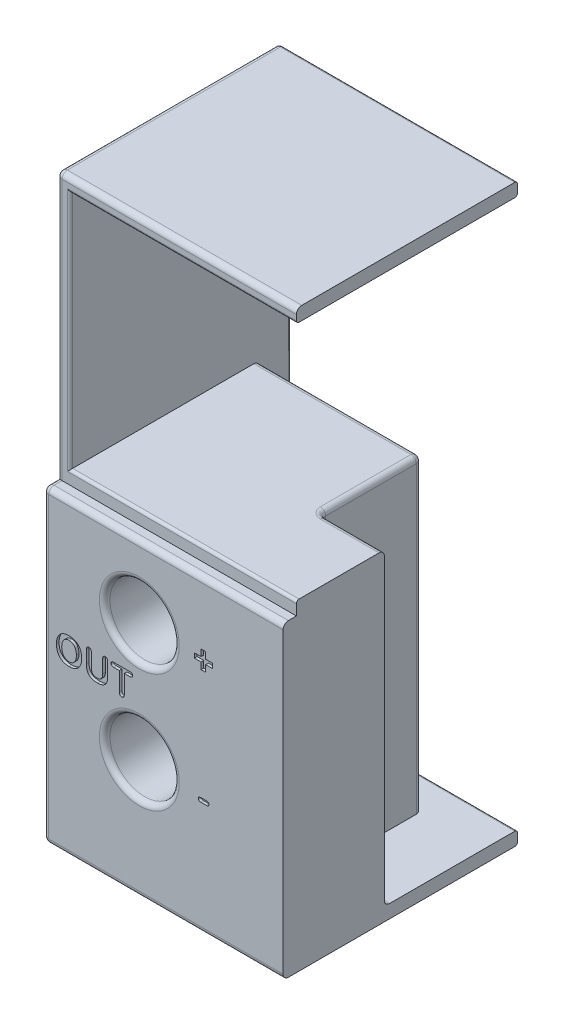
SolidWorks part; units mm, degrees
ref_plane "Front Plane" through (0, 0, 0) normal (0, 0, 1) x (1, 0, 0)
ref_plane "Top Plane" through (0, 0, 0) normal (0, 1, 0) x (1, 0, 0)
ref_plane "Right Plane" through (0, 0, 0) normal (1, 0, 0) x (0, 0, -1)
sketch "Sketch2" plane through (0, 0, 0) normal (0, 0, 1) x (1, 0, 0)
  line L0 (0, 32.5) -> (0, 0) construction
  line L1 (43.9999, -54) -> (-43.9999, -54)
  line L2 (43.9999, -54) -> (43.9999, 54)
  line L3 (43.9999, 54) -> (-43.9999, 54)
  line L4 (-43.9999, -54) -> (-43.9999, 54)
  line L5 (43.9999, -54) -> (-43.9999, 54) construction
  line L6 (43.9999, 54) -> (-43.9999, -54) construction
  line L9 (0, 0) -> (0, -20.5) construction
  line L10 (-31.75, 43.125) -> (31.75, 43.125)
  line L11 (-31.75, 43.125) -> (-31.75, 21.875)
  line L12 (-31.75, 21.875) -> (31.75, 21.875)
  line L13 (31.75, 43.125) -> (31.75, 21.875)
  line L14 (-31.75, 43.125) -> (31.75, 21.875) construction
  line L15 (-31.75, 21.875) -> (31.75, 43.125) construction
  line L16 (27, -31.625) -> (-27, -31.625)
  line L17 (27, -31.625) -> (27, -9.375)
  line L18 (27, -9.375) -> (-27, -9.375)
  line L19 (-27, -31.625) -> (-27, -9.375)
  line L20 (27, -31.625) -> (-27, -9.375) construction
  line L21 (27, -9.375) -> (-27, -31.625) construction
  circle A0 centre (-27, -9.375) radius 6.5
  circle A1 centre (27, -9.375) radius 6.5
  circle A2 centre (27, -31.625) radius 6.5
  circle A3 centre (-27, -31.625) radius 6.5
  point P0 (0, 0)
  point P5 (0, 32.5)
  point P26 (0, -20.5)
  dimension "D4" = 13
  dimension "D1" = 108
  dimension "D2" = 21.25
  dimension "D3" = 63.5
  dimension "D5" = 22.25
  dimension "D6" = 54
  dimension "D7" = 87.9997
  dimension "D8" = 32.5
  dimension "D9" = 20.5
extrude "Boss-Extrude1" add sketch "Sketch2" against normal blind 46 contours L4 L1 L2 L3 A3 L19 A0 L18 A1 L17 A2 L16 L10 L13 L12 L11 | A3 L16 A2 L17 A1 L18 A0 L19 region at (0, -1.6874, 0) region at (0, -20.5, 0)
sketch "Sketch3" plane through (0, 0, 0) normal (1, 0, 0) x (0, 0, -1)
  line L0 (46, -54) -> (0, -54) construction
  line L1 (46, 54) -> (0.0001, 54)
  line L2 (46, 54) -> (46, -54)
  line L3 (46, -54) -> (0.0001, -54)
  line L4 (0.0001, 54) -> (0.0001, -54)
  line L5 (46, 54) -> (0.0001, -54) construction
  line L6 (46, -54) -> (0.0001, 54) construction
  line L7 (46, -54) -> (46, 54) construction
  line L8 (23, -15.875) -> (23, -25.125) construction
  line L9 (30.5308, -2.875) -> (30.5308, -15.875) construction
  line L18 (34, 0.625) -> (34, -19.375)
  line L19 (34, -9.375) -> (27.5, -9.375) construction
  line L20 (36, -19.375) -> (34, -19.375)
  line L21 (36, 0.625) -> (36, -19.375)
  line L22 (36, 0.625) -> (34, 0.625)
  line L23 (34, -19.375) -> (34, 0.625)
  line L24 (19, 0.625) -> (34, 0.625)
  line L25 (19, -19.375) -> (19, 0.625)
  line L26 (19, -19.375) -> (34, -19.375)
  line L27 (46, -2.875) -> (0, -2.875) construction
  line L28 (0, -15.875) -> (46, -15.875) construction
  line L29 (46, -25.125) -> (0, -25.125) construction
  line L30 (0.0001, -20.5) -> (46, -20.5) construction
  line L31 (34, -31.625) -> (27.5, -31.625) construction
  line L32 (30.5308, -38.125) -> (30.5308, -25.125) construction
  line L33 (19, -21.625) -> (34, -21.625)
  line L34 (19, -21.625) -> (19, -41.625)
  line L35 (19, -41.625) -> (34, -41.625)
  line L36 (34, -21.625) -> (34, -41.625)
  line L37 (36, -41.625) -> (34, -41.625)
  line L38 (36, -41.625) -> (36, -21.625)
  line L39 (36, -21.625) -> (34, -21.625)
  line L40 (34, -41.625) -> (34, -21.625)
  arc A1 (34, -17.625) -> (34, -1.125) centre (35.9856, -9.375) cw
  arc A2 (34, -23.375) -> (34, -39.875) centre (35.9856, -31.625) ccw
  point P0 (23, 0)
  point P8 (30.5308, -9.375)
  point P19 (23, -20.5)
  point P48 (23, -41)
  dimension "D4" = 6.5
  dimension "D7" = 1.75
  dimension "D1" = 108
  dimension "D2" = 20
  dimension "D3" = 45.9999
  dimension "D5" = 2
  dimension "D6" = 15
  dimension "D8" = 10
sketch "Sketch4" plane through (0, 0, -46) normal (0, 0, -1) x (-1, 0, 0)
  line L1 (-31.75, 21.875) -> (31.75, 21.875)
  line L2 (-31.75, 21.875) -> (-31.75, 43.125)
  line L3 (-31.75, 43.125) -> (31.75, 43.125)
  line L4 (31.75, 21.875) -> (31.75, 43.125)
extrude "Boss-Extrude2" add sketch "Sketch4" against normal offset from surface (44 mm away) 2 up to face at (-20.5, -9.375, 0)
sketch "Sketch5" plane through (0, 0, -46) normal (0, 0, -1) x (-1, 0, 0)
  circle A0 centre (-27, -9.375) radius 6.5
  circle A1 centre (-27, -31.625) radius 6.5
  circle A2 centre (27, -31.625) radius 6.5
  circle A3 centre (27, -9.375) radius 6.5
  circle A5 centre (-27, -9.375) radius 6.5 construction
extrude "Boss-Extrude3" add sketch "Sketch5" against normal blind 10
sketch "Sketch7" plane through (0, 0, 0) normal (0, 0, 1) x (1, 0, 0)
  line L0 (-45, -54) -> (45, 54) construction
  line L1 (-45, 54) -> (45, 54)
  line L2 (-45, 54) -> (-45, -54)
  line L3 (-45, -54) -> (45, -54)
  line L4 (45, 54) -> (45, -54)
  line L5 (43.9999, 54) -> (-43.9999, 54) construction
  line L7 (-43.9999, 54) -> (43.9999, 54)
  line L8 (-43.9999, 54) -> (-43.9999, -54)
  line L9 (-43.9999, -54) -> (43.9999, -54)
  line L10 (43.9999, 54) -> (43.9999, -54)
  line M10 (-43.9999, 54) -> (-43.9999, -54)
  line M12 (43.9999, -54) -> (43.9999, 54)
  dimension "D1" = 90
extrude "Boss-Extrude4" add sketch "Sketch7" against normal up to surface (46 mm away) contours L0 L3 L4 M12 | L2 L0 L1 M10 | L10 L0 L1 | L0 L3 L8 region at (-44.5009, 0.2995, 0) region at (-44.3332, -53.5999, 0) region at (44.3332, 53.5999, 0) region at (44.5009, -0.2995, 0) up to face at (0, 0, -46)
extrude "Cut-Extrude1" cut sketch "Sketch3" along normal blind 28 from surface contours L18 A1 L24 L25 L26 | L21 L22 L18 L23 L20 | A2 L36 L33 L34 L35 | L40 A2 | L38 L39 L36 L40 L37 | A1 L23 region at (0, -9.375, -35) region at (0, -9.375, -24.7667) region at (0, -9.375, -31.2897) region at (0, -31.625, -24.7667) region at (0, -31.625, -35) region at (0, -31.625, -31.2897) starting at face at (-45, 0, -23)
extrude "Cut-Extrude2" cut sketch "Sketch3<3>" against normal blind 28 from surface contours L18 A1 L24 L25 L26 | A1 L23 | L21 L22 L18 L23 L20 | L38 L39 L36 L40 L37 | L40 A2 | A2 L36 L33 L34 L35 region at (0, -9.375, -35) region at (0, -9.375, -24.7667) region at (0, -9.375, -31.2897) region at (0, -31.625, -24.7667) region at (0, -31.625, -35) region at (0, -31.625, -31.2897) starting at face at (45, 0, -23)
sketch "Sketch3<3>" plane through (0, 0, 0) normal (1, 0, 0) x (0, 0, -1) same geometry as "Sketch3"
sketch "Sketch6" plane through (0, 0, 0) normal (0, 0, 1) x (1, 0, 0)
  line L1 (-42.5, 51.5) -> (42.5, 51.5)
  line L2 (-42.5, 51.5) -> (-42.5, 6.5)
  line L3 (-42.5, 6.5) -> (42.5, 6.5)
  line L4 (42.5, 51.5) -> (42.5, 6.5)
  line L5 (-42.5, 51.5) -> (42.5, 6.5) construction
  line L6 (-45, 54) -> (45, 54)
  line L7 (-45, 54) -> (-45, 4)
  line L8 (-45, 4) -> (45, 4)
  line L9 (45, 54) -> (45, 4)
  line L10 (45, 54) -> (-45, 4) construction
  point P9 (0, 29)
  line M13 (-31.75, 43.125) -> (31.75, 43.125)
  line M14 (31.75, 43.125) -> (31.75, 21.875)
  line M15 (31.75, 21.875) -> (-31.75, 21.875)
  line M16 (-31.75, 21.875) -> (-31.75, 43.125)
  dimension "D1" = 85
  dimension "D2" = 45
  dimension "D3" = 90
  dimension "D4" = 50
extrude "Cut-Extrude4" cut sketch "Sketch6" against normal through all contours L4 L1 L2 L3 M16 M13 M14 M15 | M13 M16 M15 M14 region at (0, 50.5382, 0) region at (0, 32.5, 0)
sketch "Sketch8" plane through (0, 0, -36) normal (0, 0, 1) x (1, 0, 0)
  circle A0 centre (-27, -9.375) radius 4.25
  circle A1 centre (-27, -31.625) radius 4.25
  circle A2 centre (27, -31.625) radius 4.25
  circle A3 centre (27, -9.375) radius 4.25
  circle A4 centre (27, -31.625) radius 6.5 construction
  circle A5 centre (27, -9.375) radius 6.5 construction
  circle A6 centre (-27, -9.375) radius 6.5 construction
  circle A7 centre (-27, -31.625) radius 6.5 construction
  dimension "D1" = 8.5
extrude "Cut-Extrude5" cut sketch "Sketch8" against normal through all
sketch "Sketch9" plane through (0, 0, -46) normal (0, 0, -1) x (-1, 0, 0)
  line L0 (0, -51.5) -> (0, -54) construction
  line L1 (-42.5, 51.5) -> (42.5, 51.5)
  line L2 (-42.5, 51.5) -> (-42.5, -51.5)
  line L3 (-42.5, -51.5) -> (42.5, -51.5)
  line L4 (42.5, 51.5) -> (42.5, -51.5)
  line L5 (-45, -54) -> (45, -54) construction
  line L6 (42.5, 0) -> (45, 0) construction
  line L7 (45, -54) -> (45, 54) construction
extrude "Cut-Extrude6" cut sketch "Sketch9" against normal blind 8
extrude "Cut-Extrude7" cut sketch "Sketch6<4>" against normal blind 2.5
sketch "Sketch6<4>" plane through (0, 0, 0) normal (0, 0, 1) x (1, 0, 0) same geometry as "Sketch6"
sketch "Sketch10" plane through (0, 0, 0) normal (1, 0, 0) x (0, 0, -1)
  line L0 (46, -54) -> (0, -54) construction
  line L1 (46, 54) -> (44, 54)
  line L2 (46, 54) -> (46, -54)
  line L3 (46, -54) -> (44, -54)
  line L4 (44, 54) -> (44, -54)
  dimension "D1" = 2
extrude "Cut-Extrude8" cut sketch "Sketch10" against normal through all both and the other way through all
fillet "Fillet2" radius 1 74 edges at (-45, -41.625, -27.5) (-45, -21.625, -27.5) (-45, -19.375, -27.5) (-45, 0.625, -27.5) (-17, -19.375, -27.5) (-17, 0.625, -27.5) (-31, -21.625, -36) (-31, -41.625, -36) (-45, -31.625, -36) (-22.75, -31.625, -36) (-31, 0.625, -36) (-17, -9.375, -36) (-31, -19.375, -36) (-45, -9.375, -36) (-22.75, -9.375, -36) (-17, -41.625, -27.5) (-17, -31.625, -36) (-17, -21.625, -27.5) (-27, -38.125, -19) (-31, -41.625, -19) (-17, -31.625, -19) (-31, -21.625, -19) (-45, -31.625, -19) (-27, -2.875, -19) (-31, -19.375, -19) (-17, -9.375, -19) (-31, 0.625, -19) (-45, -9.375, -19) (45, -19.375, -27.5) (27, -2.875, -19) (31, -19.375, -19) (45, -9.375, -19) (17, -19.375, -27.5) (17, -9.375, -19) (17, 0.625, -27.5) (31, 0.625, -19) (45, 0.625, -27.5) (31, -19.375, -36) (17, -9.375, -36) (31, 0.625, -36) (45, -9.375, -36) (31.25, -9.375, -36) (45, -41.625, -27.5) (31, -41.625, -36) (45, -31.625, -36) (31.25, -31.625, -36) (31, -21.625, -36) (45, -21.625, -27.5) (27, -38.125, -19) (31, -21.625, -19) (31, -41.625, -19) (45, -31.625, -19) (17, -31.625, -19) (17, -21.625, -27.5) (17, -31.625, -36) (17, -41.625, -27.5) (0, 6.5, -38) (45, -54, -22) (-45, -54, -22) (-45, 54, -23.25) (-45, 4, -1.25) (-45, 29, -2.5) (-45, -25, 0) (0, -54, 0) (0, 4, 0) (45, 4, -1.25) (45, -25, 0) (45, 54, -23.25) (45, 29, -2.5) (0, 54, -2.5) (-20.5, -31.625, 0) (33.5, -9.375, 0) (33.5, -31.625, 0) (-20.5, -9.375, 0)
fillet "Fillet3" radius 0.5 20 edges at (44.7071, 53.7071, -44) (0, 54, -44) (-44.7071, 53.7071, -44) (-45, 0, -44) (-44.7071, -53.7071, -44) (0, -54, -44) (44.7071, -53.7071, -44) (45, 0, -44) (42.5, 0, -44) (0, -51.5, -44) (-42.5, 0, -44) (0, 51.5, -44) (-31.25, -31.625, -38) (22.75, -9.375, -38) (22.75, -31.625, -38) (-31.25, -9.375, -38) (-42.5, 29, -2.5) (0, 6.5, -2.5) (42.5, 29, -2.5) (0, 51.5, -2.5)
sketch "Sketch11" plane through (0, 0, -38) normal (0, 0, -1) x (-1, 0, 0)
  line L0 (-42.5, 6.5) -> (42.5, 6.5) construction
  line L1 (-12, 6.5) -> (12, 6.5)
  line L2 (-12, 6.5) -> (-12, -51.5)
  line L3 (-12, -51.5) -> (12, -51.5)
  line L4 (12, 6.5) -> (12, -51.5)
  line L5 (-12, 6.5) -> (12, -51.5) construction
  line L6 (-12, -51.5) -> (12, 6.5) construction
  line L7 (-42.5, -51.5) -> (42.5, -51.5) construction
  line L8 (0, -22.5) -> (0, 0) construction
  line L9 (-17, -0.375) -> (-17, -18.375) construction
  point P0 (0, -22.5)
  dimension "D1" = 5
extrude "Cut-Extrude9" cut sketch "Sketch11" against normal up to surface (19 mm away) up to face at (-27, -1.875, -19)
fillet "Fillet4" radius 1 10 edges at (12, -23, -38) (-12, -23, -38) (12, 6.2071, -37.7071) (-12, 6.2071, -37.7071) (12, 6.5, -28) (-12, 6.5, -28) (0, -51.5, -19) (12, -22.5, -19) (0, 6.5, -19) (-12, -22.5, -19)
sketch "Sketch12" plane through (0, 0, 0) normal (0, 0, 1) x (1, 0, 0)
  line L0 (-27, -9.375) -> (-27, -31.625) construction
  line L1 (-19.5, -9.375) -> (-19.5, -31.625) construction
  line L4 (-19.5, -20.5) -> (-44, -20.5) construction
  line L5 (-44, 3) -> (-44, -53) construction
  line L6 (-27, -9.375) -> (-19.5, -9.375) construction
  line L7 (-44, -23) -> (-27, -23) construction
  line L8 (27, -9.375) -> (27, -31.625) construction
  line L9 (-19.9289, -11.875) -> (-9.9289, -11.875) construction
  line L11 (-19.5, -9.375) -> (27, -9.375) construction
  line L12 (-19.5, -31.625) -> (27, -31.625) construction
  line L13 (-9.9289, -11.875) -> (9.9289, -11.875) construction
  line L14 (-19.9289, -34.125) -> (-9.9289, -34.125) construction
  line L15 (-19.9289, -11.875) -> (-19.9289, -34.125) construction
  line L16 (-27, -23) -> (27, -23) construction
  line L17 (27, -23) -> (44, -23) construction
  line L18 (44, -53) -> (44, 3) construction
  line L19 (9.9289, -11.875) -> (19.9289, -11.875) construction
  line L20 (19.9289, -11.875) -> (19.9289, -34.125) construction
  line L21 (-9.9289, -34.125) -> (9.9289, -34.125) construction
  line L22 (9.9289, -34.125) -> (19.9289, -34.125) construction
  line L23 (0, -11.875) -> (0, -34.125) construction
  circle A0 centre (-27, -9.375) radius 7.5 construction
  circle A1 centre (-27, -31.625) radius 7.5 construction
  circle A2 centre (27, -31.625) radius 7.5 construction
  circle A4 centre (27, -9.375) radius 7.5 construction
  text T0 "OUT" font "Arial Rounded MT Bold" height 5
  text T1 "IN" font "Arial Rounded MT Bold" height 5
  text T2 "+" font "Arial Rounded MT Bold" height 5
  text T3 "-" font "Arial Rounded MT Bold" height 5
  text T4 "+" font "Arial Rounded MT Bold" height 5
  text T5 "-" font "Arial Rounded MT Bold" height 5
  point P10 (-27, -20.5)
  dimension "D1" = 2.5
  dimension "D2" = 2.5
  dimension "D3" = 10
  dimension "D4" = 10
extrude "Cut-Extrude10" cut sketch "Sketch12" against normal blind 0.5
sketch "Sketch13" plane through (0, 0, 0) normal (0, 0, 1) x (1, 0, 0)
  line L0 (44, -54) -> (-44, -54) construction
  line L1 (-45, 54) -> (0, 54)
  line L2 (-45, 54) -> (-45, -54)
  line L3 (-45, -54) -> (0, -54)
  line L4 (0, 54) -> (0, -54)
  line L5 (45, 3) -> (45, -53) construction
  line L6 (0, 54) -> (45, 54)
  line L7 (0, 54) -> (0, -54)
  line L8 (0, -54) -> (45, -54)
  line L9 (45, 54) -> (45, -54)
  line L10 (-45, -53) -> (-45, 3) construction
  line L11 (-44, 54) -> (44, 54) construction
extrude "Cut-Extrude12" cut sketch "Sketch13" against normal through all contours L9 L6 L4 L8 region at (22.5, 0, 0)
